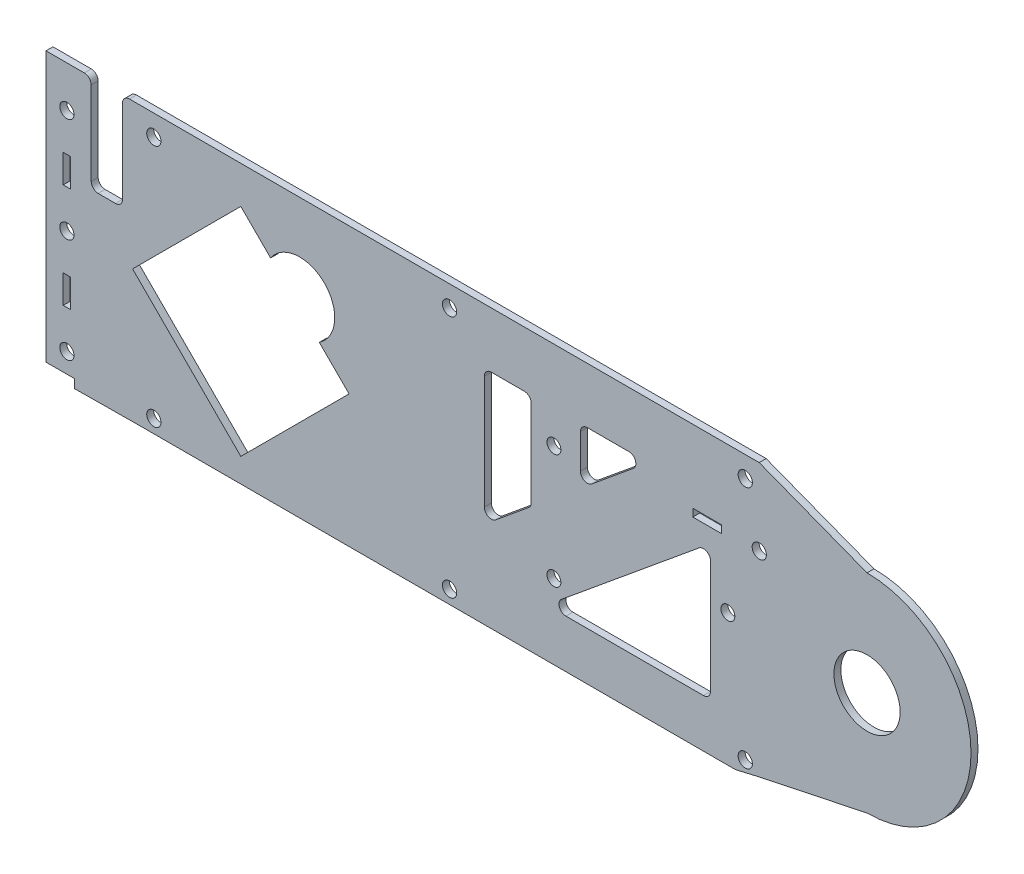
SolidWorks part; units mm, degrees
ref_plane "前视基准面" through (0, 0, 0) normal (0, 0, 1) x (1, 0, 0)
ref_plane "上视基准面" through (0, 0, 0) normal (0, 1, 0) x (1, 0, 0)
ref_plane "右视基准面" through (0, 0, 0) normal (1, 0, 0) x (0, 0, -1)
sketch "草图1" plane through (0, 0, 0) normal (0, 0, 1) x (1, 0, 0)
  line L0 (0.5429, 31.9043) -> (0.5429, 27.8043)
  line L1 (0.5429, 18.7543) -> (0.5429, 10.9543) construction
  line L2 (-0.5071, 10.8043) -> (1.5929, 10.8043)
  line L3 (-0.5071, 10.8043) -> (-0.5071, 18.9043)
  line L4 (-0.5071, 18.9043) -> (1.5929, 18.9043)
  line L5 (1.5929, 10.8043) -> (1.5929, 18.9043)
  line L6 (-0.5071, 10.8043) -> (1.5929, 18.9043) construction
  line L7 (-0.5071, 18.9043) -> (1.5929, 10.8043) construction
  line L12 (0.5429, -0.1457) -> (-5.3571, -0.1457) construction
  line L18 (50.5429, -0.1457) -> (97.8433, -0.1457) construction
  line L19 (50.5429, -0.1457) -> (230.5429, -0.1457) construction
  line L20 (200.6429, -0.1457) -> (200.6429, 38.1043) construction
  line L42 (230.5429, -30.0457) -> (199.5561, -36.5559)
  line L47 (2.6929, -38.2957) -> (-5.4571, -38.2957)
  line L49 (-5.4571, 41.7043) -> (7.5429, 41.7043)
  line L54 (199.5429, 41.7043) -> (230.5429, 29.7543)
  line L55 (7.5429, 41.7043) -> (7.5429, 13.7043)
  line L57 (7.5429, 13.7043) -> (16.5429, 13.7043)
  line L59 (-5.4571, 41.7043) -> (261.5429, 41.7043) construction
  line L60 (16.5429, 41.7043) -> (199.5429, 41.7043)
  line L61 (16.5429, 41.7043) -> (16.5429, 13.7043)
  line L62 (50.5429, 13.8543) -> (59.0992, 22.4106) construction
  line L63 (64.5429, -0.1457) -> (73.0992, 8.4106) construction
  line L64 (59.0992, 22.4106) -> (50.5429, 30.967)
  line L65 (19.4302, -0.1457) -> (50.5429, 30.967)
  line L66 (19.4302, -0.1457) -> (50.5429, -31.2584)
  line L67 (50.5429, -31.2584) -> (81.6556, -0.1457)
  line L68 (50.5429, 30.967) -> (81.6556, -0.1457) construction
  line L69 (19.4302, -0.1457) -> (81.6556, -0.1457) construction
  line L70 (50.5429, -31.2584) -> (50.5429, 30.967) construction
  line L71 (73.0992, 8.4106) -> (81.6556, -0.1457)
  line L72 (0.5429, -0.1457) -> (50.5429, -0.1457) construction
  line L73 (-0.5071, -19.1957) -> (1.5929, -11.0957) construction
  line L74 (-0.5071, -11.0957) -> (1.5929, -19.1957) construction
  line L75 (0.5429, -19.0457) -> (0.5429, -11.2457) construction
  line L76 (1.5929, -11.0957) -> (1.5929, -19.1957)
  line L77 (-0.5071, -19.1957) -> (1.5929, -19.1957)
  line L78 (-0.5071, -11.0957) -> (-0.5071, -19.1957)
  line L79 (-0.5071, -11.0957) -> (1.5929, -11.0957)
  line L80 (199.5561, -36.5559) -> (192.7469, -38.1457)
  line L81 (192.7469, -38.1457) -> (21.3658, -38.1457)
  line L82 (21.3658, -38.1457) -> (2.6929, -38.2957)
  line L83 (-5.4571, 41.7043) -> (-5.4571, -35.8026)
  line L84 (-5.4571, -35.8026) -> (2.6929, -35.8026)
  line L85 (2.6929, -35.8026) -> (2.6929, -38.2957)
  circle A0 centre (0.5429, 29.8543) radius 2.05
  circle A1 centre (0.5429, -0.1457) radius 2.05
  circle A2 centre (0.5429, -30.1457) radius 2.05
  circle A15 centre (230.5429, -0.1457) radius 9.525
  circle A16 centre (230.5429, -0.1457) radius 29.9 construction
  arc A17 (230.5429, -30.0457) -> (230.5429, 29.7543) centre (230.5429, -0.1457) ccw
  arc A19 (59.0992, 22.4106) -> (73.0992, 8.4106) centre (67.4545, 16.7659) cw
  point P6 (0.5429, 14.8543)
  point P25 (50.5429, -0.1457)
  point P67 (0.5429, -15.1457)
  dimension "D3" = 44
  dimension "D4" = 44
  dimension "D13" = 19.05
  dimension "D1" = 8.1
  dimension "D2" = 2.1
  dimension "D5" = 50
  dimension "D7" = 15
  dimension "D8" = 60
  dimension "D9" = 30
  dimension "D14" = 180
extrude "凸台-拉伸1" add sketch "草图1" along normal blind 2 contours A2 A1 A0 L5 L2 L3 L4 region at (128.7391, 1.2876, 0)
sketch "草图3" plane through (0, 0, 2) normal (0, 0, 1) x (1, 0, 0)
  line L0 (16.5429, 41.7043) -> (199.5429, 41.7043) construction
  line L1 (16.5429, 41.7043) -> (16.5429, 13.7043) construction
  line L2 (148.1533, 25.7043) -> (148.1533, 9.6322)
  line L3 (110.5429, -34.2957) -> (195.5429, 35.7043) construction
  line L4 (195.5429, 35.7043) -> (195.5429, -34.2957) construction
  line L5 (195.5429, -34.2957) -> (110.5429, -34.2957) construction
  line L6 (185.5429, -24.2957) -> (138.4162, -24.2957)
  line L7 (138.4162, -24.2957) -> (185.5429, 14.5145)
  line L8 (185.5429, 14.5145) -> (185.5429, -24.2957)
  line L9 (110.5429, -34.2957) -> (110.5429, 35.7043) construction
  line L10 (110.5429, 35.7043) -> (195.5429, 35.7043) construction
  line L11 (120.5429, 25.7043) -> (167.6695, 25.7043) construction
  line L12 (120.5429, -13.1059) -> (167.6695, 25.7043) construction
  line L13 (120.5429, -13.1059) -> (120.5429, 25.7043)
  line L15 (134.0149, 25.7043) -> (134.0149, -2.0113)
  line L17 (134.0149, 25.7043) -> (120.5429, 25.7043)
  line L19 (134.0149, -2.0113) -> (120.5429, -13.1059)
  line L21 (148.1533, 25.7043) -> (167.6695, 25.7043)
  line L22 (167.6695, 25.7043) -> (148.1533, 9.6322)
  line L23 (199.574, 19.7043) -> (184.574, 19.7043) construction
  line L24 (16.5429, 41.7043) -> (199.5429, 41.7043) construction
  line L25 (188.674, 20.8043) -> (180.474, 20.8043)
  line L26 (188.674, 20.8043) -> (188.674, 18.6043)
  line L27 (188.674, 18.6043) -> (180.474, 18.6043)
  line L28 (180.474, 20.8043) -> (180.474, 18.6043)
  line L29 (188.674, 20.8043) -> (180.474, 18.6043) construction
  line L30 (188.674, 18.6043) -> (180.474, 20.8043) construction
  circle A0 centre (25.5429, 35.7043) radius 2.05
  circle A1 centre (110.5429, 35.7043) radius 2.05
  circle A2 centre (195.5429, 35.7043) radius 2.05
  circle A3 centre (110.5429, -34.2957) radius 2.05
  circle A4 centre (195.5429, -34.2957) radius 2.05
  circle A5 centre (25.5429, -34.2957) radius 2.05
  circle A6 centre (190.5429, -0.1457) radius 2
  circle A7 centre (140.5429, 16.3543) radius 2
  circle A8 centre (140.5429, -16.6457) radius 2
  circle A9 centre (230.5429, -0.1457) radius 2 construction
  circle A10 centre (199.574, 19.7043) radius 2.05
  dimension "D1" = 6
  dimension "D7" = 15
  dimension "D2" = 9
  dimension "D8" = 2.2
  dimension "D9" = 8.2
  dimension "D10" = 22
  dimension "D5" = 10
  dimension "D6" = 10
  dimension "D3" = 3
  dimension "D4" = 2
fillet "圆角1" radius 2 4 edges at (16.5429, 41.7043, 1) (7.5429, 41.7043, 1) (7.5429, 13.7043, 1) (16.5429, 13.7043, 1)
extrude "切除-拉伸1" cut sketch "草图3" against normal blind 2
fillet "圆角2" radius 2 10 edges at (134.0149, -2.0113, 1) (134.0149, 25.7043, 1) (120.5429, 25.7043, 1) (120.5429, -13.1059, 1) (185.5429, -24.2957, 1) (185.5429, 14.5145, 1) (138.4162, -24.2957, 1) (148.1533, 9.6322, 1) (148.1533, 25.7043, 1) (167.6695, 25.7043, 1)
